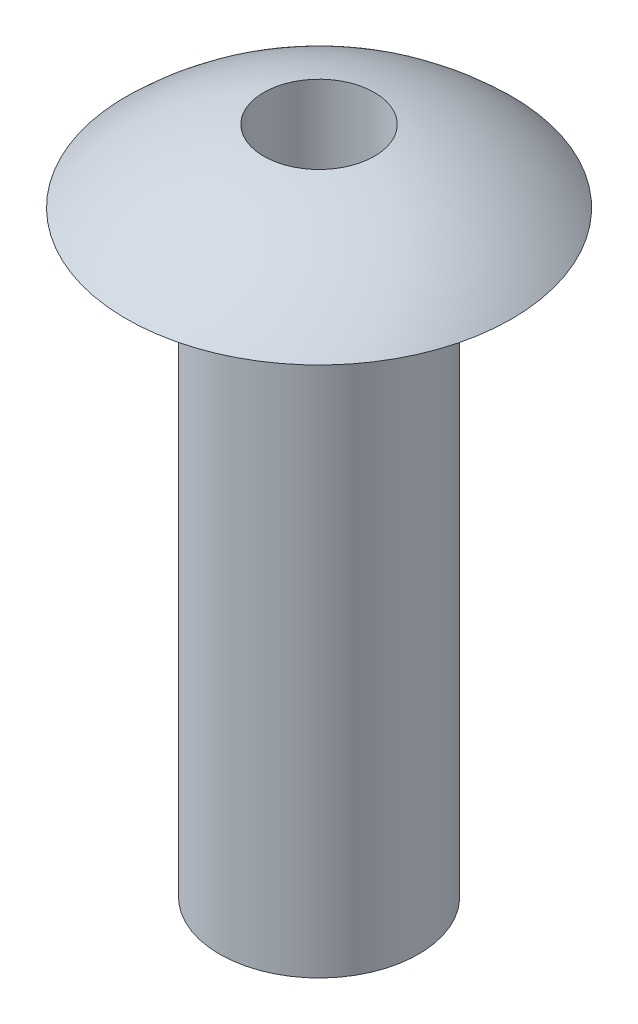
SolidWorks part; units mm, degrees
ref_plane "Front Plane" through (0, 0, 0) normal (0, 0, 1) x (1, 0, 0)
ref_plane "Top Plane" through (0, 0, 0) normal (0, 1, 0) x (1, 0, 0)
ref_plane "Right Plane" through (0, 0, 0) normal (1, 0, 0) x (0, 0, -1)
ref_axis "X-Axis" through (-88.99, 0, 0) along (1, 0, 0)
ref_axis "Y-Axis" through (0, 55, 0) along (0, -1, 0)
ref_axis "Z-Axis" through (0, 0, -88.99) along (0, 0, 1)
sketch "Sketch1" plane through (0, 0, 0) normal (0, 0, 1) x (1, 0, 0)
  line L0 (0, 0) -> (1.6, 0)
  line L1 (1.6, 0) -> (1.6, 9.6)
  line L2 (1.6, 9.6) -> (3.1, 9.6)
  line L3 (0, 0) -> (0, 10.85)
  arc A0 (0, 10.85) -> (3.1, 9.6) centre (0, 6.381) cw
  dimension "D1" = 9.6
  dimension "D2" = 1.5
  dimension "D3" = 1.25
  dimension "D4" = 1.6
revolve "Revolve1" add sketch "Sketch1" angle 360 about L3
sketch "Sketch2" plane through (0, 0, 0) normal (0, -1, 0) x (1, 0, 0)
  circle A0 centre (0, 0) radius 0.89
  dimension "D1" = 1.78
extrude "Cut-Extrude1" cut sketch "Sketch2" against normal through all
equation "\"D2@Sketch1\"=(6.2-3.2)/2"
equation "\"D4@Sketch1\"=3.2/2"
